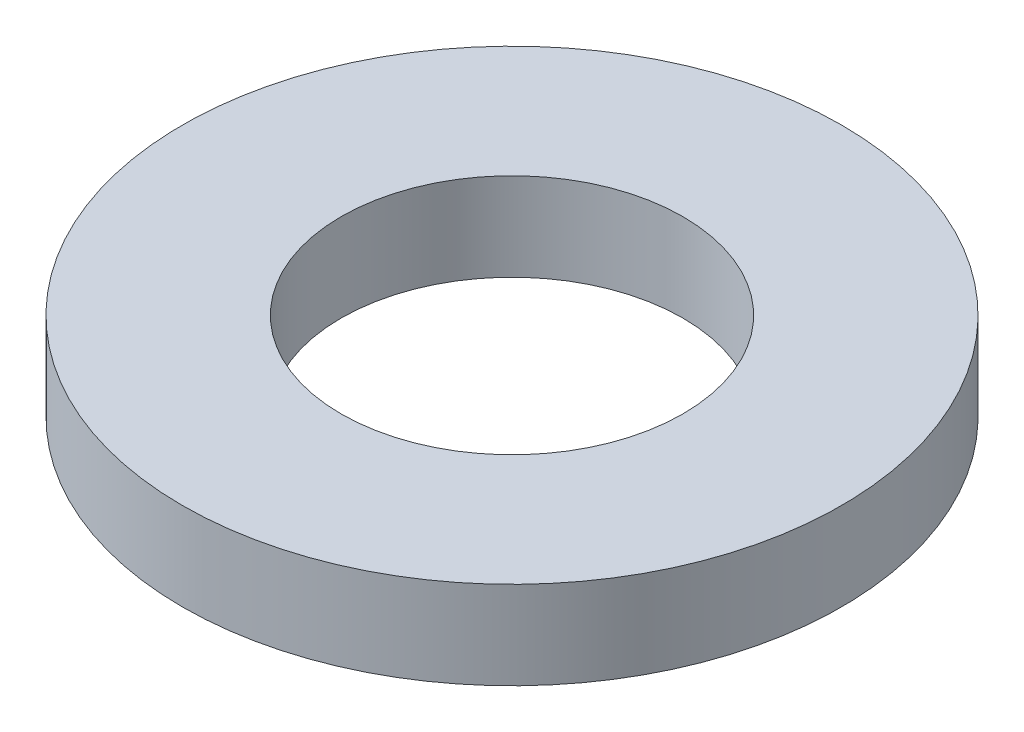
SolidWorks part; units mm, degrees
ref_plane "Front Plane" through (0, 0, 0) normal (0, 0, 1) x (1, 0, 0)
ref_plane "Top Plane" through (0, 0, 0) normal (0, 1, 0) x (1, 0, 0)
ref_plane "Right Plane" through (0, 0, 0) normal (1, 0, 0) x (0, 0, -1)
sketch "Sketch1" plane through (0, 0, 0) normal (0, 1, 0) x (1, 0, 0)
  circle A0 centre (0, 0) radius 67.5
  dimension "FLANGE_OD" = 135
extrude "Boss-Extrude1" add sketch "Sketch1" along normal blind 18
sketch "Sketch2" plane through (0, 0, 0) normal (0, 1, 0) x (1, 0, 0)
  circle A0 centre (0, 0) radius 35
  dimension "BORE_D" = 70
extrude "Cut-Extrude1" cut sketch "Sketch2" along normal through all
sketch "Sketch3" plane through (0, 18, 0) normal (0, 1, 0) x (1, 0, 0)
  circle A0 centre (0, 0) radius 23.0551 construction
  circle A1 centre (-23.0551, 0) radius 4.2369
  dimension "BOLT_D" = 8.4738
  dimension "BOLT_PCD" = 46.1103
extrude "Cut-Extrude2" cut sketch "Sketch3" against normal blind 17.3859 rebuild error yes
pattern_circular "CirPattern1" count 5 over 360 rebuild error yes
